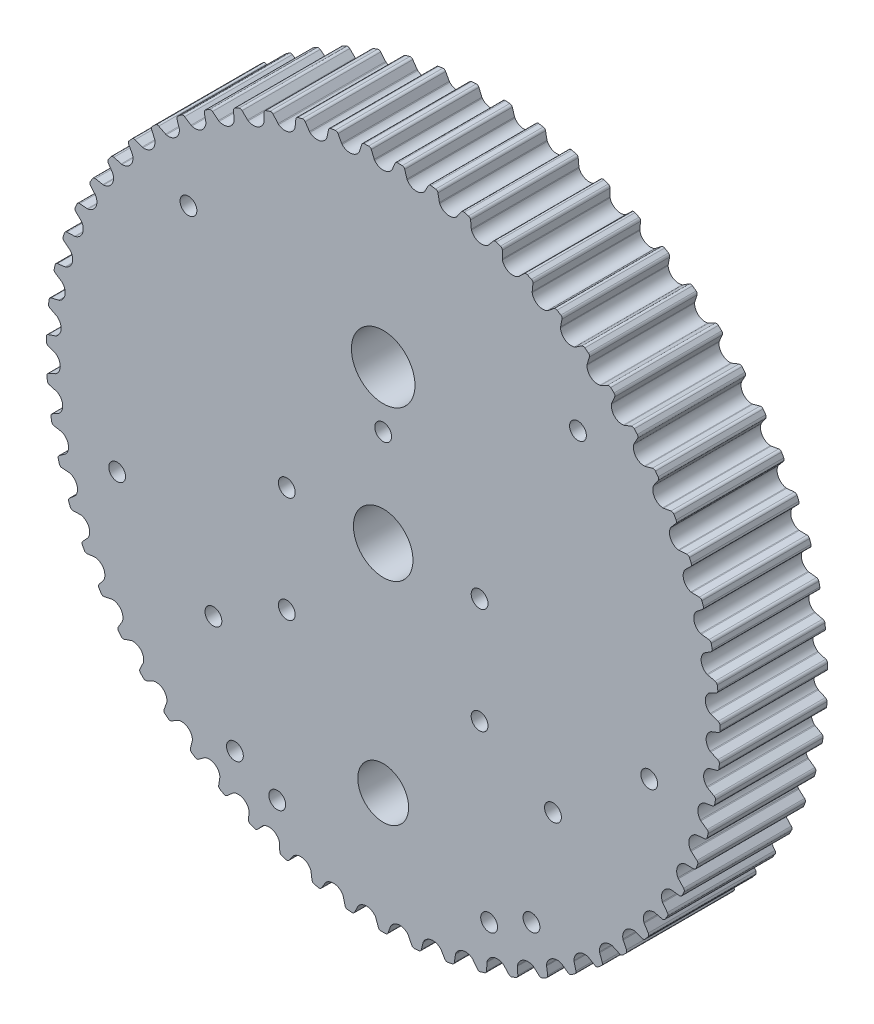
SolidWorks part; units mm, degrees
material "PETG"
ref_plane "Front Plane" through (0, 0, 0) normal (0, 0, 1) x (1, 0, 0)
ref_plane "Top Plane" through (0, 0, 0) normal (0, 1, 0) x (1, 0, 0)
ref_plane "Right Plane" through (0, 0, 0) normal (1, 0, 0) x (0, 0, -1)
sketch "Sketch1" plane through (0, 0, 0) normal (0, 0, 1) x (1, 0, 0)
  line L0 (0, 0) -> (0, 50000) construction
  line L1 (0, 0) -> (3.9983, 80.1144) construction
  line L2 (0, 0) -> (-3.9983, 80.1144) construction
  line L3 (-2.1085, 77.3973) -> (-2.8064, 79.0584)
  line L4 (2.1085, 77.3973) -> (2.8064, 79.0584)
  line L5 (5.6082, 77.2226) -> (5.0793, 78.9449)
  line L6 (9.8043, 76.8027) -> (10.6641, 78.3861)
  line L7 (13.2692, 76.2805) -> (12.9144, 78.0469)
  line L8 (17.4027, 75.4449) -> (18.4158, 76.9348)
  line L9 (20.7984, 74.5802) -> (20.6212, 76.3732)
  line L10 (24.8281, 73.3372) -> (25.9846, 74.7188)
  line L11 (28.1208, 72.1388) -> (28.123, 73.9405)
  line L12 (32.0068, 70.5007) -> (33.295, 71.7603)
  line L13 (35.1638, 68.9804) -> (35.3454, 70.7729)
  line L14 (38.8673, 66.9635) -> (40.2746, 68.0886)
  line L15 (41.8573, 65.1364) -> (42.2164, 66.902)
  line L16 (45.3416, 62.7608) -> (46.8539, 63.7402)
  line L17 (48.1348, 60.6451) -> (48.6679, 62.3661)
  line L18 (51.3652, 57.9344) -> (52.9675, 58.7583)
  line L19 (53.9339, 55.551) -> (54.6358, 57.2105)
  line L20 (56.8784, 52.5322) -> (58.5548, 53.1925)
  line L21 (59.197, 49.9049) -> (60.0606, 51.4862)
  line L22 (61.8263, 46.6079) -> (63.5601, 47.098)
  line L23 (63.8717, 43.7628) -> (64.8885, 45.2502)
  line L24 (66.1597, 40.2204) -> (67.9337, 40.5354)
  line L25 (67.9117, 37.1858) -> (69.0715, 38.5646)
  line L26 (69.8356, 33.4331) -> (71.6321, 33.57)
  line L27 (71.2767, 30.2392) -> (72.5681, 31.4956)
  line L28 (72.8174, 26.3136) -> (74.6186, 26.2709)
  line L29 (73.9334, 22.992) -> (75.3434, 24.1137)
  line L30 (75.0756, 18.9326) -> (76.8636, 18.7107)
  line L31 (75.8553, 15.5164) -> (77.37, 16.4921)
  line L32 (76.5876, 11.3634) -> (78.3446, 10.9646)
  line L33 (77.0233, 7.8865) -> (78.6276, 8.7066)
  line L34 (77.3384, 3.6813) -> (79.047, 3.1095)
  line L35 (77.4258, 0.1783) -> (79.1038, 0.8345)
  line L36 (77.3206, -4.0374) -> (78.9638, -4.7765)
  line L37 (77.0588, -7.5317) -> (78.7938, -7.0458)
  line L38 (76.5344, -11.716) -> (78.0959, -12.615)
  line L39 (75.9259, -15.1668) -> (77.7007, -14.8561)
  line L40 (74.9876, -19.2782) -> (76.4517, -20.3281)
  line L41 (74.0385, -22.6513) -> (75.8354, -22.5188)
  line L42 (72.6954, -26.6487) -> (74.0478, -27.8393)
  line L43 (71.4153, -29.9106) -> (73.2164, -29.9577)
  line L44 (69.6808, -33.7544) -> (70.908, -35.0737)
  line L45 (68.0823, -36.8726) -> (69.8697, -37.0988)
  line L46 (65.9737, -40.5247) -> (67.0634, -41.9596)
  line L47 (64.0726, -43.4682) -> (65.8287, -43.8712)
  line L48 (61.6109, -46.8922) -> (62.5523, -48.4284)
  line L49 (59.4262, -49.6317) -> (61.1334, -50.2076)
  line L50 (56.6358, -52.7936) -> (57.4196, -54.416)
  line L51 (54.1892, -55.302) -> (55.8306, -56.0451)
  line L52 (51.0978, -58.1704) -> (51.7161, -59.8627)
  line L53 (48.4136, -60.4227) -> (49.9728, -61.3255)
  line L54 (45.052, -62.969) -> (45.4988, -64.7145)
  line L55 (42.1568, -64.9429) -> (43.6185, -65.9965)
  line L56 (38.5585, -67.1418) -> (38.8292, -68.9231)
  line L57 (35.4811, -68.8177) -> (36.8306, -70.0115)
  line L58 (31.6817, -70.6474) -> (31.7737, -72.4468)
  line L59 (28.4528, -72.0085) -> (29.6767, -73.3307)
  line L60 (24.49, -73.4508) -> (24.4024, -75.2504)
  line L61 (21.1417, -74.4836) -> (22.2278, -75.9212)
  line L62 (17.055, -75.5242) -> (16.7887, -77.3062)
  line L63 (13.6204, -76.2185) -> (14.5581, -77.7571)
  line L64 (9.4505, -76.8471) -> (9.008, -78.5936)
  line L65 (5.9638, -77.1959) -> (6.7436, -78.8202)
  line L66 (1.752, -77.4061) -> (1.1379, -79.1)
  line L67 (-1.752, -77.4061) -> (-1.1379, -79.1)
  line L68 (-5.9638, -77.1959) -> (-6.7436, -78.8202)
  line L69 (-9.4505, -76.8471) -> (-9.008, -78.5936)
  line L70 (-13.6204, -76.2185) -> (-14.5581, -77.7571)
  line L71 (-17.055, -75.5242) -> (-16.7887, -77.3062)
  line L72 (-21.1417, -74.4836) -> (-22.2278, -75.9212)
  line L73 (-24.49, -73.4508) -> (-24.4024, -75.2504)
  line L74 (-28.4528, -72.0085) -> (-29.6767, -73.3307)
  line L75 (-31.6817, -70.6474) -> (-31.7737, -72.4468)
  line L76 (-35.4811, -68.8177) -> (-36.8306, -70.0115)
  line L77 (-38.5585, -67.1418) -> (-38.8292, -68.9231)
  line L78 (-42.1568, -64.9429) -> (-43.6185, -65.9965)
  line L79 (-45.052, -62.969) -> (-45.4988, -64.7145)
  line L80 (-48.4136, -60.4227) -> (-49.9728, -61.3255)
  line L81 (-51.0978, -58.1704) -> (-51.7161, -59.8627)
  line L82 (-54.1892, -55.302) -> (-55.8306, -56.0451)
  line L83 (-56.6358, -52.7936) -> (-57.4196, -54.416)
  line L84 (-59.4262, -49.6317) -> (-61.1334, -50.2076)
  line L85 (-61.6109, -46.8922) -> (-62.5523, -48.4284)
  line L86 (-64.0726, -43.4682) -> (-65.8287, -43.8712)
  line L87 (-65.9737, -40.5247) -> (-67.0634, -41.9596)
  line L88 (-68.0823, -36.8726) -> (-69.8697, -37.0988)
  line L89 (-69.6808, -33.7544) -> (-70.908, -35.0737)
  line L90 (-71.4153, -29.9106) -> (-73.2164, -29.9577)
  line L91 (-72.6954, -26.6487) -> (-74.0478, -27.8393)
  line L92 (-74.0385, -22.6513) -> (-75.8354, -22.5188)
  line L93 (-74.9876, -19.2782) -> (-76.4517, -20.3281)
  line L94 (-75.9259, -15.1668) -> (-77.7007, -14.8561)
  line L95 (-76.5344, -11.716) -> (-78.0959, -12.615)
  line L96 (-77.0588, -7.5317) -> (-78.7938, -7.0458)
  line L97 (-77.3206, -4.0374) -> (-78.9638, -4.7765)
  line L98 (-77.4258, 0.1783) -> (-79.1038, 0.8345)
  line L99 (-77.3384, 3.6813) -> (-79.047, 3.1095)
  line L100 (-77.0233, 7.8865) -> (-78.6276, 8.7066)
  line L101 (-76.5876, 11.3634) -> (-78.3446, 10.9646)
  line L102 (-75.8553, 15.5164) -> (-77.37, 16.4921)
  line L103 (-75.0756, 18.9326) -> (-76.8636, 18.7107)
  line L104 (-73.9334, 22.992) -> (-75.3434, 24.1137)
  line L105 (-72.8174, 26.3136) -> (-74.6186, 26.2709)
  line L106 (-71.2767, 30.2392) -> (-72.5681, 31.4956)
  line L107 (-69.8356, 33.4331) -> (-71.6321, 33.57)
  line L108 (-67.9117, 37.1858) -> (-69.0715, 38.5646)
  line L109 (-66.1597, 40.2204) -> (-67.9337, 40.5354)
  line L110 (-63.8717, 43.7628) -> (-64.8885, 45.2502)
  line L111 (-61.8263, 46.6079) -> (-63.5601, 47.098)
  line L112 (-59.197, 49.9049) -> (-60.0606, 51.4862)
  line L113 (-56.8784, 52.5322) -> (-58.5548, 53.1925)
  line L114 (-53.9339, 55.551) -> (-54.6358, 57.2105)
  line L115 (-51.3652, 57.9344) -> (-52.9675, 58.7583)
  line L116 (-48.1348, 60.6451) -> (-48.6679, 62.3661)
  line L117 (-45.3416, 62.7608) -> (-46.8539, 63.7402)
  line L118 (-41.8573, 65.1364) -> (-42.2164, 66.902)
  line L119 (-38.8673, 66.9635) -> (-40.2746, 68.0886)
  line L120 (-35.1638, 68.9804) -> (-35.3454, 70.7729)
  line L121 (-32.0068, 70.5007) -> (-33.295, 71.7603)
  line L122 (-28.1208, 72.1388) -> (-28.123, 73.9405)
  line L123 (0, 0) -> (2.0086, 77.226) construction
  line L124 (-24.8281, 73.3372) -> (-25.9846, 74.7188)
  line L125 (-20.7984, 74.5802) -> (-20.6212, 76.3732)
  line L126 (-17.4027, 75.4449) -> (-18.4158, 76.9348)
  line L127 (-13.2692, 76.2805) -> (-12.9144, 78.0469)
  line L128 (-9.8043, 76.8027) -> (-10.6641, 78.3861)
  line L129 (-5.6082, 77.2226) -> (-5.0793, 78.9449)
  circle A0 centre (0, 0) radius 80.2141 construction
  circle A317 centre (0, 0) radius 79.53 construction
  arc A318 (-2.0086, 77.226) -> (2.0086, 77.226) centre (0, 78.7807) ccw
  arc A319 (-2.0086, 77.226) -> (-2.1085, 77.3973) centre (-1.406, 77.6924) cw
  arc A320 (-2.8064, 79.0584) -> (-3.4334, 79.4559) centre (-3.4054, 78.8067) ccw
  arc A321 (-3.4334, 79.4559) -> (-3.9642, 79.4311) centre (0, 0) ccw
  arc A322 (3.4334, 79.4559) -> (3.9642, 79.4311) centre (0, 0) cw
  arc A323 (2.8064, 79.0584) -> (3.4334, 79.4559) centre (3.4054, 78.8067) cw
  arc A324 (2.0086, 77.226) -> (2.1085, 77.3973) centre (1.406, 77.6924) ccw
  arc A325 (4.4949, 79.4029) -> (3.9642, 79.4311) centre (0, 0) ccw
  arc A326 (5.0793, 78.9449) -> (4.4949, 79.4029) centre (4.4582, 78.7542) ccw
  arc A327 (5.6906, 77.0422) -> (9.6878, 76.6422) centre (7.844, 78.3892) ccw
  arc A328 (5.6906, 77.0422) -> (5.6082, 77.2226) centre (6.3366, 77.4463) cw
  arc A329 (9.6878, 76.6422) -> (9.8043, 76.8027) centre (9.1347, 77.1663) ccw
  arc A330 (10.6641, 78.3861) -> (11.3276, 78.7192) centre (11.2351, 78.0761) cw
  arc A331 (11.3276, 78.7192) -> (11.8533, 78.6417) centre (0, 0) cw
  arc A332 (12.3785, 78.5608) -> (11.8533, 78.6417) centre (0, 0) ccw
  arc A333 (12.9144, 78.0469) -> (12.3785, 78.5608) centre (12.2774, 77.919) ccw
  arc A334 (13.3333, 76.0928) -> (17.2708, 75.2968) centre (15.6101, 77.2187) ccw
  arc A335 (13.3333, 76.0928) -> (13.2692, 76.2805) centre (14.0163, 76.4305) cw
  arc A336 (17.2708, 75.2968) -> (17.4027, 75.4449) centre (16.7726, 75.8733) ccw
  arc A337 (18.4158, 76.9348) -> (19.1092, 77.2001) centre (18.9531, 76.5694) cw
  arc A338 (19.1092, 77.2001) -> (19.6246, 77.0707) centre (0, 0) cw
  arc A339 (20.1391, 76.9379) -> (19.6246, 77.0707) centre (0, 0) ccw
  arc A340 (20.6212, 76.3732) -> (20.1391, 76.9379) centre (19.9746, 76.3093) ccw
  arc A341 (20.8434, 74.3871) -> (24.6821, 73.203) centre (23.221, 75.2807) ccw
  arc A342 (20.8434, 74.3871) -> (20.7984, 74.5802) centre (21.5567, 74.6552) cw
  arc A343 (24.6821, 73.203) -> (24.8281, 73.3372) centre (24.2438, 73.8263) ccw
  arc A344 (25.9846, 74.7188) -> (26.7009, 74.9138) centre (26.4828, 74.3018) cw
  arc A345 (26.7009, 74.9138) -> (27.2009, 74.7338) centre (0, 0) cw
  arc A346 (27.6996, 74.5503) -> (27.2009, 74.7338) centre (0, 0) ccw
  arc A347 (28.123, 73.9405) -> (27.6996, 74.5503) centre (27.4733, 73.9413) ccw
  arc A348 (28.1464, 71.9421) -> (31.8481, 70.3817) centre (30.6012, 72.5945) ccw
  arc A349 (28.1464, 71.9421) -> (28.1208, 72.1388) centre (28.8828, 72.1378) cw
  arc A350 (31.8481, 70.3817) -> (32.0068, 70.5007) centre (31.474, 71.0455) ccw
  arc A351 (33.295, 71.7603) -> (34.0272, 71.883) centre (33.7493, 71.2958) cw
  arc A352 (34.0272, 71.883) -> (34.5068, 71.6541) centre (0, 0) cw
  arc A353 (34.9848, 71.4219) -> (34.5068, 71.6541) centre (0, 0) ccw
  arc A354 (35.3454, 70.7729) -> (34.9848, 71.4219) centre (34.699, 70.8384) ccw
  arc A355 (35.1696, 68.7821) -> (38.6976, 66.8609) centre (37.6772, 69.1869) ccw
  arc A356 (35.1696, 68.7821) -> (35.1638, 68.9804) centre (35.9219, 68.9036) cw
  arc A357 (38.6976, 66.8609) -> (38.8673, 66.9635) centre (38.3915, 67.5587) ccw
  arc A358 (40.2746, 68.0886) -> (41.0154, 68.1378) centre (40.6803, 67.5811) cw
  arc A359 (41.0154, 68.1378) -> (41.4697, 67.8622) centre (0, 0) cw
  arc A360 (41.9222, 67.5836) -> (41.4697, 67.8622) centre (0, 0) ccw
  arc A361 (42.2164, 66.902) -> (41.9222, 67.5836) centre (41.5798, 67.0315) ccw
  arc A362 (41.8434, 64.9386) -> (45.1625, 62.6756) centre (44.3787, 65.0917) ccw
  arc A363 (41.8434, 64.9386) -> (41.8573, 65.1364) centre (42.604, 64.9845) cw
  arc A364 (45.1625, 62.6756) -> (45.3416, 62.7608) centre (44.9274, 63.4004) ccw
  arc A365 (46.8539, 63.7402) -> (47.5959, 63.7154) centre (47.2071, 63.1949) cw
  arc A366 (47.5959, 63.7154) -> (48.0206, 63.3959) centre (0, 0) cw
  arc A367 (48.4431, 63.0737) -> (48.0206, 63.3959) centre (0, 0) ccw
  arc A368 (48.6679, 62.3661) -> (48.4431, 63.0737) centre (48.0473, 62.5584) ccw
  arc A369 (48.1012, 60.4496) -> (51.1786, 57.8674) centre (50.6393, 60.3495) ccw
  arc A370 (48.1012, 60.4496) -> (48.1348, 60.6451) centre (48.8626, 60.4196) cw
  arc A371 (51.1786, 57.8674) -> (51.3652, 57.9344) centre (51.0168, 58.6121) ccw
  arc A372 (52.9675, 58.7583) -> (53.7034, 58.6597) centre (53.2647, 58.1805) cw
  arc A373 (53.7034, 58.6597) -> (54.0941, 58.2996) centre (0, 0) cw
  arc A374 (54.4825, 57.9369) -> (54.0941, 58.2996) centre (0, 0) ccw
  arc A375 (54.6358, 57.2105) -> (54.4825, 57.9369) centre (54.0374, 57.4636) ccw
  arc A376 (53.881, 55.3599) -> (56.686, 52.4841) centre (56.3965, 55.0076) ccw
  arc A377 (53.881, 55.3599) -> (53.9339, 55.551) centre (54.6357, 55.2542) cw
  arc A378 (56.686, 52.4841) -> (56.8784, 52.5322) centre (56.5991, 53.2412) ccw
  arc A379 (58.5548, 53.1925) -> (59.2772, 53.0211) centre (58.7929, 52.588) cw
  arc A380 (59.2772, 53.0211) -> (59.6301, 52.6239) centre (0, 0) cw
  arc A381 (59.9804, 52.2243) -> (59.6301, 52.6239) centre (0, 0) ccw
  arc A382 (60.0606, 51.4862) -> (59.9804, 52.2243) centre (59.4904, 51.7976) ccw
  arc A383 (59.1254, 49.72) -> (61.63, 46.5792) centre (61.5932, 49.119) ccw
  arc A384 (59.1254, 49.72) -> (59.197, 49.9049) centre (59.8657, 49.5397) cw
  arc A385 (61.63, 46.5792) -> (61.8263, 46.6079) centre (61.619, 47.3411) ccw
  arc A386 (63.5601, 47.098) -> (64.2618, 46.8555) centre (63.7368, 46.4728) cw
  arc A387 (64.2618, 46.8555) -> (64.5734, 46.4251) centre (0, 0) cw
  arc A388 (64.8822, 45.9926) -> (64.5734, 46.4251) centre (0, 0) ccw
  arc A389 (64.8885, 45.2502) -> (64.8822, 45.9926) centre (64.3521, 45.6169) ccw
  arc A390 (63.7821, 43.5859) -> (65.9616, 40.2114) centre (66.1778, 42.7422) ccw
  arc A391 (63.7821, 43.5859) -> (63.8717, 43.7628) centre (64.5008, 43.3328) cw
  arc A392 (65.9616, 40.2114) -> (66.1597, 40.2204) centre (66.0264, 40.9706) ccw
  arc A393 (67.9337, 40.5354) -> (68.6078, 40.2243) centre (68.0473, 39.8957) cw
  arc A394 (68.6078, 40.2243) -> (68.875, 39.765) centre (0, 0) cw
  arc A395 (69.1392, 39.3039) -> (68.875, 39.765) centre (0, 0) ccw
  arc A396 (69.0715, 38.5646) -> (69.1392, 39.3039) centre (68.5743, 38.9828) ccw
  arc A397 (67.8049, 37.0187) -> (69.6375, 33.4439) centre (70.1047, 35.9406) ccw
  arc A398 (67.8049, 37.0187) -> (67.9117, 37.1858) centre (68.4948, 36.6953) cw
  arc A399 (69.6375, 33.4439) -> (69.8356, 33.4331) centre (69.7777, 34.1929) ccw
  arc A400 (71.6321, 33.57) -> (72.2719, 33.1933) centre (71.6815, 32.9221) cw
  arc A401 (72.2719, 33.1933) -> (72.4921, 32.7097) centre (0, 0) cw
  arc A402 (72.709, 32.2246) -> (72.4921, 32.7097) centre (0, 0) ccw
  arc A403 (72.5681, 31.4956) -> (72.709, 32.2246) centre (72.115, 31.9613) ccw
  arc A404 (71.1538, 30.0836) -> (72.6214, 26.3441) centre (73.3349, 28.7818) ccw
  arc A405 (71.1538, 30.0836) -> (71.2767, 30.2392) centre (71.8081, 29.693) cw
  arc A406 (72.6214, 26.3441) -> (72.8174, 26.3136) centre (72.8355, 27.0754) ccw
  arc A407 (74.6186, 26.2709) -> (75.2177, 25.8324) centre (74.6032, 25.6214) cw
  arc A408 (75.2177, 25.8324) -> (75.3887, 25.3292) centre (0, 0) cw
  arc A409 (75.5562, 24.825) -> (75.3887, 25.3292) centre (0, 0) ccw
  arc A410 (75.3434, 24.1137) -> (75.5562, 24.825) centre (74.939, 24.6222) ccw
  arc A411 (73.7956, 22.8494) -> (74.8836, 18.9824) centre (75.8362, 21.337) ccw
  arc A412 (73.7956, 22.8494) -> (73.9334, 22.992) centre (74.4078, 22.3957) cw
  arc A413 (74.8836, 18.9824) -> (75.0756, 18.9326) centre (75.1694, 19.6888) ccw
  arc A414 (76.8636, 18.7107) -> (77.416, 18.2148) centre (76.7836, 18.066) cw
  arc A415 (77.416, 18.2148) -> (77.536, 17.6971) centre (0, 0) cw
  arc A416 (77.6525, 17.1786) -> (77.536, 17.6971) centre (0, 0) ccw
  arc A417 (77.37, 16.4921) -> (77.6525, 17.1786) centre (77.0181, 17.0383) ccw
  arc A418 (75.7039, 15.3882) -> (76.4015, 11.4321) centre (77.5838, 13.6801) ccw
  arc A419 (75.7039, 15.3882) -> (75.8553, 15.5164) centre (76.2679, 14.8758) cw
  arc A420 (76.4015, 11.4321) -> (76.5876, 11.3634) centre (76.7562, 12.1065) ccw
  arc A421 (78.3446, 10.9646) -> (78.8449, 10.4161) centre (78.2008, 10.331) cw
  arc A422 (78.8449, 10.4161) -> (78.9128, 9.8891) centre (0, 0) cw
  arc A423 (78.9771, 9.3616) -> (78.9128, 9.8891) centre (0, 0) ccw
  arc A424 (78.6276, 8.7066) -> (78.9771, 9.3616) centre (78.3319, 9.2851) ccw
  arc A425 (76.8599, 7.7741) -> (77.1601, 3.7681) centre (78.5604, 5.8873) ccw
  arc A426 (76.8599, 7.7741) -> (77.0233, 7.8865) centre (77.3701, 7.208) cw
  arc A427 (77.1601, 3.7681) -> (77.3384, 3.6813) centre (77.5802, 4.4039) ccw
  arc A428 (79.047, 3.1095) -> (79.4903, 2.5139) centre (78.8409, 2.4934) cw
  arc A429 (79.4903, 2.5139) -> (79.5053, 1.9827) centre (0, 0) cw
  arc A430 (79.5168, 1.4515) -> (79.5053, 1.9827) centre (0, 0) ccw
  arc A431 (79.1038, 0.8345) -> (79.5168, 1.4515) centre (78.8671, 1.4396) ccw
  arc A432 (77.252, 0.0827) -> (77.1519, -3.9333) centre (78.7562, -1.9641) ccw
  arc A433 (77.252, 0.0827) -> (77.4258, 0.1783) centre (77.7033, -0.5314) cw
  arc A434 (77.1519, -3.9333) -> (77.3206, -4.0374) centre (77.6332, -3.3425) ccw
  arc A435 (78.9638, -4.7765) -> (79.3456, -5.4133) centre (78.6973, -5.369) cw
  arc A436 (79.3456, -5.4133) -> (79.3076, -5.9433) centre (0, 0) cw
  arc A437 (79.2661, -6.4731) -> (79.3076, -5.9433) centre (0, 0) ccw
  arc A438 (78.7938, -7.0458) -> (79.2661, -6.4731) centre (78.6186, -6.4202) ccw
  arc A439 (76.8764, -7.6096) -> (76.3769, -11.5956) centre (78.1693, -9.7959) ccw
  arc A440 (76.8764, -7.6096) -> (77.0588, -7.5317) centre (77.2643, -8.2655) cw
  arc A441 (76.3769, -11.5956) -> (76.5344, -11.716) centre (76.9146, -11.0557) ccw
  arc A442 (78.0959, -12.615) -> (78.4123, -13.2866) centre (77.7717, -13.1781) cw
  arc A443 (78.4123, -13.2866) -> (78.3218, -13.8102) centre (0, 0) cw
  arc A444 (78.2277, -14.3332) -> (78.3218, -13.8102) centre (0, 0) ccw
  arc A445 (77.7007, -14.8561) -> (78.2277, -14.3332) centre (77.5887, -14.2161) ccw
  arc A446 (75.7367, -15.2262) -> (74.8428, -19.1426) centre (76.8055, -17.5304) ccw
  arc A447 (75.7367, -15.2262) -> (75.9259, -15.1668) centre (76.0573, -15.9174) cw
  arc A448 (74.8428, -19.1426) -> (74.9876, -19.2782) centre (75.4316, -18.6589) ccw
  arc A449 (76.4517, -20.3281) -> (76.6997, -21.0279) centre (76.0731, -20.8561) cw
  arc A450 (76.6997, -21.0279) -> (76.5575, -21.5399) centre (0, 0) cw
  arc A451 (76.4119, -22.051) -> (76.5575, -21.5399) centre (0, 0) ccw
  arc A452 (75.8354, -22.5188) -> (76.4119, -22.051) centre (75.7876, -21.8708) ccw
  arc A453 (73.8443, -22.6914) -> (72.5649, -26.4994) centre (74.6784, -25.0906) ccw
  arc A454 (73.8443, -22.6914) -> (74.0385, -22.6513) centre (74.0945, -23.4112) cw
  arc A455 (72.5649, -26.4994) -> (72.6954, -26.6487) centre (73.1989, -26.0768) ccw
  arc A456 (74.0478, -27.8393) -> (74.2249, -28.5603) centre (73.6185, -28.3269) cw
  arc A457 (74.2249, -28.5603) -> (74.0324, -29.0556) centre (0, 0) cw
  arc A458 (73.8366, -29.5496) -> (74.0324, -29.0556) centre (0, 0) ccw
  arc A459 (73.2164, -29.9577) -> (73.8366, -29.5496) centre (73.2334, -29.3082) ccw
  arc A460 (71.218, -29.9312) -> (69.5658, -33.5929) centre (71.8091, -32.4015) ccw
  arc A461 (71.218, -29.9312) -> (71.4153, -29.9106) centre (71.3953, -30.6723) cw
  arc A462 (69.5658, -33.5929) -> (69.6808, -33.7544) centre (70.2388, -33.2355) ccw
  arc A463 (70.908, -35.0737) -> (71.0123, -35.8088) centre (70.4322, -35.5162) cw
  arc A464 (71.0123, -35.8088) -> (70.7715, -36.2824) centre (0, 0) cw
  arc A465 (70.5275, -36.7545) -> (70.7715, -36.2824) centre (0, 0) ccw
  arc A466 (69.8697, -37.0988) -> (70.5275, -36.7545) centre (69.9513, -36.4542) ccw
  arc A467 (67.8839, -36.8735) -> (65.8754, -40.3525) centre (68.2261, -39.3903) ccw
  arc A468 (67.8839, -36.8735) -> (68.0823, -36.8726) centre (67.9866, -37.6286) cw
  arc A469 (65.8754, -40.3525) -> (65.9737, -40.5247) centre (66.5806, -40.0638) ccw
  arc A470 (67.0634, -41.9596) -> (67.0941, -42.7014) centre (66.5459, -42.3525) cw
  arc A471 (67.0941, -42.7014) -> (66.8073, -43.1487) centre (0, 0) cw
  arc A472 (66.5175, -43.5941) -> (66.8073, -43.1487) centre (0, 0) ccw
  arc A473 (65.8287, -43.8712) -> (66.5175, -43.5941) centre (65.974, -43.238) ccw
  arc A474 (63.8752, -43.4493) -> (61.5302, -46.711) centre (63.965, -45.9877) ccw
  arc A475 (63.8752, -43.4493) -> (64.0726, -43.4682) centre (63.9021, -44.2108) cw
  arc A476 (61.5302, -46.711) -> (61.6109, -46.8922) centre (62.2607, -46.494) ccw
  arc A477 (62.5523, -48.4284) -> (62.509, -49.1696) centre (61.9983, -48.7679) cw
  arc A478 (62.509, -49.1696) -> (62.1791, -49.5861) centre (0, 0) cw
  arc A479 (61.8464, -50.0005) -> (62.1791, -49.5861) centre (0, 0) ccw
  arc A480 (61.1334, -50.2076) -> (61.8464, -50.0005) centre (61.3411, -49.592) ccw
  arc A481 (59.2316, -49.5933) -> (56.5735, -52.6053) centre (59.0683, -52.1281) ccw
  arc A482 (59.2316, -49.5933) -> (59.4262, -49.6317) centre (59.1826, -50.3538) cw
  arc A483 (56.5735, -52.6053) -> (56.6358, -52.7936) centre (57.322, -52.4621) ccw
  arc A484 (57.4196, -54.416) -> (57.3027, -55.1491) centre (56.8345, -54.6986) cw
  arc A485 (57.3027, -55.1491) -> (56.9329, -55.5308) centre (0, 0) cw
  arc A486 (56.5606, -55.9099) -> (56.9329, -55.5308) centre (0, 0) ccw
  arc A487 (55.8306, -56.0451) -> (56.5606, -55.9099) centre (56.0985, -55.4532) ccw
  arc A488 (53.9994, -55.2445) -> (51.0546, -57.9768) centre (53.5845, -57.7503) ccw
  arc A489 (53.9994, -55.2445) -> (54.1892, -55.302) centre (53.8749, -55.9962) cw
  arc A490 (51.0546, -57.9768) -> (51.0978, -58.1704) centre (51.8136, -57.9089) ccw
  arc A491 (51.7161, -59.8627) -> (51.5268, -60.5806) centre (51.1059, -60.0857) cw
  arc A492 (51.5268, -60.5806) -> (51.1209, -60.9235) centre (0, 0) cw
  arc A493 (50.7127, -61.2637) -> (51.1209, -60.9235) centre (0, 0) ccw
  arc A494 (49.9728, -61.3255) -> (50.7127, -61.2637) centre (50.2984, -60.7632) ccw
  arc A495 (48.2305, -60.3465) -> (45.0283, -62.7721) centre (47.5681, -62.7987) ccw
  arc A496 (48.2305, -60.3465) -> (48.4136, -60.4227) centre (48.0318, -61.0822) cw
  arc A497 (45.0283, -62.7721) -> (45.052, -62.969) centre (45.7902, -62.7801) ccw
  arc A498 (45.4988, -64.7145) -> (45.2389, -65.41) centre (44.8693, -64.8756) cw
  arc A499 (45.2389, -65.41) -> (44.8008, -65.7108) centre (0, 0) cw
  arc A500 (44.3608, -66.0086) -> (44.8008, -65.7108) centre (0, 0) ccw
  arc A501 (43.6185, -65.9965) -> (44.3608, -66.0086) centre (43.9984, -65.4694) ccw
  arc A502 (41.9822, -64.8489) -> (38.5544, -66.9436) centre (41.079, -67.2229) ccw
  arc A503 (41.9822, -64.8489) -> (42.1568, -64.9429) centre (41.7113, -65.5611) cw
  arc A504 (38.5544, -66.9436) -> (38.5585, -67.1418) centre (39.3118, -67.0273) ccw
  arc A505 (38.8292, -68.9231) -> (38.5014, -69.5893) centre (38.1868, -69.0208) cw
  arc A506 (38.5014, -69.5893) -> (38.0355, -69.845) centre (0, 0) cw
  arc A507 (37.568, -70.0975) -> (38.0355, -69.845) centre (0, 0) ccw
  arc A508 (36.8306, -70.0115) -> (37.568, -70.0975) centre (37.2611, -69.5249) ccw
  arc A509 (35.3168, -68.7067) -> (31.6974, -70.4497) centre (34.1817, -70.979) ccw
  arc A510 (35.3168, -68.7067) -> (35.4811, -68.8177) centre (34.9762, -69.3884) cw
  arc A511 (31.6974, -70.4497) -> (31.6817, -70.6474) centre (32.4427, -70.6085) ccw
  arc A512 (31.7737, -72.4468) -> (31.3812, -73.077) centre (31.1248, -72.48) cw
  arc A513 (31.3812, -73.077) -> (30.8922, -73.285) centre (0, 0) cw
  arc A514 (30.4019, -73.4898) -> (30.8922, -73.285) centre (0, 0) ccw
  arc A515 (29.6767, -73.3307) -> (30.4019, -73.4898) centre (30.1535, -72.8894) ccw
  arc A516 (28.3003, -71.8817) -> (24.5254, -73.2556) centre (26.9446, -74.0296) ccw
  arc A517 (28.3003, -71.8817) -> (28.4528, -72.0085) centre (27.8936, -72.5261) cw
  arc A518 (24.5254, -73.2556) -> (24.49, -73.4508) centre (25.2511, -73.4878) ccw
  arc A519 (24.4024, -75.2504) -> (23.9491, -75.8384) centre (23.7535, -75.2188) cw
  arc A520 (23.9491, -75.8384) -> (23.4419, -75.9967) centre (0, 0) cw
  arc A521 (22.9336, -76.1516) -> (23.4419, -75.9967) centre (0, 0) ccw
  arc A522 (22.2278, -75.9212) -> (22.9336, -76.1516) centre (22.7462, -75.5295) ccw
  arc A523 (21.0026, -74.3423) -> (17.1096, -75.3336) centre (19.4397, -76.3446) ccw
  arc A524 (21.0026, -74.3423) -> (21.1417, -74.4836) centre (20.5337, -74.943) cw
  arc A525 (17.1096, -75.3336) -> (17.055, -75.5242) centre (17.8086, -75.6369) ccw
  arc A526 (16.7887, -77.3062) -> (16.2791, -77.8461) centre (16.1461, -77.2101) cw
  arc A527 (16.2791, -77.8461) -> (15.7586, -77.9531) centre (0, 0) cw
  arc A528 (15.2374, -78.0567) -> (15.7586, -77.9531) centre (0, 0) ccw
  arc A529 (14.5581, -77.7571) -> (15.2374, -78.0567) centre (15.1129, -77.419) ccw
  arc A530 (13.4961, -76.0641) -> (9.5238, -76.6628) centre (11.7417, -77.9008) ccw
  arc A531 (13.4961, -76.0641) -> (13.6204, -76.2185) centre (12.9698, -76.6151) cw
  arc A532 (9.5238, -76.6628) -> (9.4505, -76.8471) centre (10.1891, -77.0342) ccw
  arc A533 (9.008, -78.5936) -> (8.4472, -79.0801) centre (8.3782, -78.4341) cw
  arc A534 (8.4472, -79.0801) -> (7.9186, -79.1348) centre (0, 0) cw
  arc A535 (7.3897, -79.1859) -> (7.9186, -79.1348) centre (0, 0) ccw
  arc A536 (6.7436, -78.8202) -> (7.3897, -79.1859) centre (7.3293, -78.539) ccw
  arc A537 (5.8555, -77.0298) -> (1.8433, -77.2301) centre (3.9269, -78.6828) ccw
  arc A538 (5.8555, -77.0298) -> (5.9638, -77.1959) centre (5.2769, -77.5257) cw
  arc A539 (1.8433, -77.2301) -> (1.752, -77.4061) centre (2.4684, -77.6659) ccw
  arc A540 (1.1379, -79.1) -> (0.5314, -79.5282) centre (0.527, -78.8785) cw
  arc A541 (0.5314, -79.5282) -> (0, -79.53) centre (0, 0) cw
  arc A542 (-0.5314, -79.5282) -> (0, -79.53) centre (0, 0) ccw
  arc A543 (-1.1379, -79.1) -> (-0.5314, -79.5282) centre (-0.527, -78.8785) ccw
  arc A544 (-1.8433, -77.2301) -> (-5.8555, -77.0298) centre (-3.9269, -78.6828) ccw
  arc A545 (-1.8433, -77.2301) -> (-1.752, -77.4061) centre (-2.4684, -77.6659) cw
  arc A546 (-5.8555, -77.0298) -> (-5.9638, -77.1959) centre (-5.2769, -77.5257) ccw
  arc A547 (-6.7436, -78.8202) -> (-7.3897, -79.1859) centre (-7.3293, -78.539) cw
  arc A548 (-7.3897, -79.1859) -> (-7.9186, -79.1348) centre (0, 0) cw
  arc A549 (-8.4472, -79.0801) -> (-7.9186, -79.1348) centre (0, 0) ccw
  arc A550 (-9.008, -78.5936) -> (-8.4472, -79.0801) centre (-8.3782, -78.4341) ccw
  arc A551 (-9.5238, -76.6628) -> (-13.4961, -76.0641) centre (-11.7417, -77.9008) ccw
  arc A552 (-9.5238, -76.6628) -> (-9.4505, -76.8471) centre (-10.1891, -77.0342) cw
  arc A553 (-13.4961, -76.0641) -> (-13.6204, -76.2185) centre (-12.9698, -76.6151) ccw
  arc A554 (-14.5581, -77.7571) -> (-15.2374, -78.0567) centre (-15.1129, -77.419) cw
  arc A555 (-15.2374, -78.0567) -> (-15.7586, -77.9531) centre (0, 0) cw
  arc A556 (-16.2791, -77.8461) -> (-15.7586, -77.9531) centre (0, 0) ccw
  arc A557 (-16.7887, -77.3062) -> (-16.2791, -77.8461) centre (-16.1461, -77.2101) ccw
  arc A558 (-17.1096, -75.3336) -> (-21.0026, -74.3423) centre (-19.4397, -76.3446) ccw
  arc A559 (-17.1096, -75.3336) -> (-17.055, -75.5242) centre (-17.8086, -75.6369) cw
  arc A560 (-21.0026, -74.3423) -> (-21.1417, -74.4836) centre (-20.5337, -74.943) ccw
  arc A561 (-22.2278, -75.9212) -> (-22.9336, -76.1516) centre (-22.7462, -75.5295) cw
  arc A562 (-22.9336, -76.1516) -> (-23.4419, -75.9967) centre (0, 0) cw
  arc A563 (-23.9491, -75.8384) -> (-23.4419, -75.9967) centre (0, 0) ccw
  arc A564 (-24.4024, -75.2504) -> (-23.9491, -75.8384) centre (-23.7535, -75.2188) ccw
  arc A565 (-24.5254, -73.2556) -> (-28.3003, -71.8817) centre (-26.9446, -74.0296) ccw
  arc A566 (-24.5254, -73.2556) -> (-24.49, -73.4508) centre (-25.2511, -73.4878) cw
  arc A567 (-28.3003, -71.8817) -> (-28.4528, -72.0085) centre (-27.8936, -72.5261) ccw
  arc A568 (-29.6767, -73.3307) -> (-30.4019, -73.4898) centre (-30.1535, -72.8894) cw
  arc A569 (-30.4019, -73.4898) -> (-30.8922, -73.285) centre (0, 0) cw
  arc A570 (-31.3812, -73.077) -> (-30.8922, -73.285) centre (0, 0) ccw
  arc A571 (-31.7737, -72.4468) -> (-31.3812, -73.077) centre (-31.1248, -72.48) ccw
  arc A572 (-31.6974, -70.4497) -> (-35.3168, -68.7067) centre (-34.1817, -70.979) ccw
  arc A573 (-31.6974, -70.4497) -> (-31.6817, -70.6474) centre (-32.4427, -70.6085) cw
  arc A574 (-35.3168, -68.7067) -> (-35.4811, -68.8177) centre (-34.9762, -69.3884) ccw
  arc A575 (-36.8306, -70.0115) -> (-37.568, -70.0975) centre (-37.2611, -69.5249) cw
  arc A576 (-37.568, -70.0975) -> (-38.0355, -69.845) centre (0, 0) cw
  arc A577 (-38.5014, -69.5893) -> (-38.0355, -69.845) centre (0, 0) ccw
  arc A578 (-38.8292, -68.9231) -> (-38.5014, -69.5893) centre (-38.1868, -69.0208) ccw
  arc A579 (-38.5544, -66.9436) -> (-41.9822, -64.8489) centre (-41.079, -67.2229) ccw
  arc A580 (-38.5544, -66.9436) -> (-38.5585, -67.1418) centre (-39.3118, -67.0273) cw
  arc A581 (-41.9822, -64.8489) -> (-42.1568, -64.9429) centre (-41.7113, -65.5611) ccw
  arc A582 (-43.6185, -65.9965) -> (-44.3608, -66.0086) centre (-43.9984, -65.4694) cw
  arc A583 (-44.3608, -66.0086) -> (-44.8008, -65.7108) centre (0, 0) cw
  arc A584 (-45.2389, -65.41) -> (-44.8008, -65.7108) centre (0, 0) ccw
  arc A585 (-45.4988, -64.7145) -> (-45.2389, -65.41) centre (-44.8693, -64.8756) ccw
  arc A586 (-45.0283, -62.7721) -> (-48.2305, -60.3465) centre (-47.5681, -62.7987) ccw
  arc A587 (-45.0283, -62.7721) -> (-45.052, -62.969) centre (-45.7902, -62.7801) cw
  arc A588 (-48.2305, -60.3465) -> (-48.4136, -60.4227) centre (-48.0318, -61.0822) ccw
  arc A589 (-49.9728, -61.3255) -> (-50.7127, -61.2637) centre (-50.2984, -60.7632) cw
  arc A590 (-50.7127, -61.2637) -> (-51.1209, -60.9235) centre (0, 0) cw
  arc A591 (-51.5268, -60.5806) -> (-51.1209, -60.9235) centre (0, 0) ccw
  arc A592 (-51.7161, -59.8627) -> (-51.5268, -60.5806) centre (-51.1059, -60.0857) ccw
  arc A593 (-51.0546, -57.9768) -> (-53.9994, -55.2445) centre (-53.5845, -57.7503) ccw
  arc A594 (-51.0546, -57.9768) -> (-51.0978, -58.1704) centre (-51.8136, -57.9089) cw
  arc A595 (-53.9994, -55.2445) -> (-54.1892, -55.302) centre (-53.8749, -55.9962) ccw
  arc A596 (-55.8306, -56.0451) -> (-56.5606, -55.9099) centre (-56.0985, -55.4532) cw
  arc A597 (-56.5606, -55.9099) -> (-56.9329, -55.5308) centre (0, 0) cw
  arc A598 (-57.3027, -55.1491) -> (-56.9329, -55.5308) centre (0, 0) ccw
  arc A599 (-57.4196, -54.416) -> (-57.3027, -55.1491) centre (-56.8345, -54.6986) ccw
  arc A600 (-56.5735, -52.6053) -> (-59.2316, -49.5933) centre (-59.0683, -52.1281) ccw
  arc A601 (-56.5735, -52.6053) -> (-56.6358, -52.7936) centre (-57.322, -52.4621) cw
  arc A602 (-59.2316, -49.5933) -> (-59.4262, -49.6317) centre (-59.1826, -50.3538) ccw
  arc A603 (-61.1334, -50.2076) -> (-61.8464, -50.0005) centre (-61.3411, -49.592) cw
  arc A604 (-61.8464, -50.0005) -> (-62.1791, -49.5861) centre (0, 0) cw
  arc A605 (-62.509, -49.1696) -> (-62.1791, -49.5861) centre (0, 0) ccw
  arc A606 (-62.5523, -48.4284) -> (-62.509, -49.1696) centre (-61.9983, -48.7679) ccw
  arc A607 (-61.5302, -46.711) -> (-63.8752, -43.4493) centre (-63.965, -45.9877) ccw
  arc A608 (-61.5302, -46.711) -> (-61.6109, -46.8922) centre (-62.2607, -46.494) cw
  arc A609 (-63.8752, -43.4493) -> (-64.0726, -43.4682) centre (-63.9021, -44.2108) ccw
  arc A610 (-65.8287, -43.8712) -> (-66.5175, -43.5941) centre (-65.974, -43.238) cw
  arc A611 (-66.5175, -43.5941) -> (-66.8073, -43.1487) centre (0, 0) cw
  arc A612 (-67.0941, -42.7014) -> (-66.8073, -43.1487) centre (0, 0) ccw
  arc A613 (-67.0634, -41.9596) -> (-67.0941, -42.7014) centre (-66.5459, -42.3525) ccw
  arc A614 (-65.8754, -40.3525) -> (-67.8839, -36.8735) centre (-68.2261, -39.3904) ccw
  arc A615 (-65.8754, -40.3525) -> (-65.9737, -40.5247) centre (-66.5806, -40.0638) cw
  arc A616 (-67.8839, -36.8735) -> (-68.0823, -36.8726) centre (-67.9866, -37.6286) ccw
  arc A617 (-69.8697, -37.0988) -> (-70.5275, -36.7545) centre (-69.9513, -36.4542) cw
  arc A618 (-70.5275, -36.7545) -> (-70.7715, -36.2824) centre (0, 0) cw
  arc A619 (-71.0123, -35.8088) -> (-70.7715, -36.2824) centre (0, 0) ccw
  arc A620 (-70.908, -35.0737) -> (-71.0123, -35.8088) centre (-70.4322, -35.5162) ccw
  arc A621 (-69.5658, -33.5929) -> (-71.218, -29.9312) centre (-71.8091, -32.4015) ccw
  arc A622 (-69.5658, -33.5929) -> (-69.6808, -33.7544) centre (-70.2388, -33.2355) cw
  arc A623 (-71.218, -29.9312) -> (-71.4153, -29.9106) centre (-71.3953, -30.6723) ccw
  arc A624 (-73.2164, -29.9577) -> (-73.8366, -29.5496) centre (-73.2334, -29.3082) cw
  arc A625 (-73.8366, -29.5496) -> (-74.0324, -29.0556) centre (0, 0) cw
  arc A626 (-74.2249, -28.5603) -> (-74.0324, -29.0556) centre (0, 0) ccw
  arc A627 (-74.0478, -27.8393) -> (-74.2249, -28.5603) centre (-73.6185, -28.3269) ccw
  arc A628 (-72.5649, -26.4994) -> (-73.8443, -22.6914) centre (-74.6784, -25.0906) ccw
  arc A629 (-72.5649, -26.4994) -> (-72.6954, -26.6487) centre (-73.1989, -26.0768) cw
  arc A630 (-73.8443, -22.6914) -> (-74.0385, -22.6513) centre (-74.0945, -23.4112) ccw
  arc A631 (-75.8354, -22.5188) -> (-76.4119, -22.051) centre (-75.7876, -21.8708) cw
  arc A632 (-76.4119, -22.051) -> (-76.5575, -21.5399) centre (0, 0) cw
  arc A633 (-76.6997, -21.0279) -> (-76.5575, -21.5399) centre (0, 0) ccw
  arc A634 (-76.4517, -20.3281) -> (-76.6997, -21.0279) centre (-76.0731, -20.8561) ccw
  arc A635 (-74.8428, -19.1426) -> (-75.7367, -15.2262) centre (-76.8055, -17.5304) ccw
  arc A636 (-74.8428, -19.1426) -> (-74.9876, -19.2782) centre (-75.4316, -18.6589) cw
  arc A637 (-75.7367, -15.2262) -> (-75.9259, -15.1668) centre (-76.0573, -15.9174) ccw
  arc A638 (-77.7007, -14.8561) -> (-78.2277, -14.3332) centre (-77.5887, -14.2161) cw
  arc A639 (-78.2277, -14.3332) -> (-78.3218, -13.8102) centre (0, 0) cw
  arc A640 (-78.4123, -13.2866) -> (-78.3218, -13.8102) centre (0, 0) ccw
  arc A641 (-78.0959, -12.615) -> (-78.4123, -13.2866) centre (-77.7717, -13.1781) ccw
  arc A642 (-76.3769, -11.5956) -> (-76.8764, -7.6096) centre (-78.1693, -9.7959) ccw
  arc A643 (-76.3769, -11.5956) -> (-76.5344, -11.716) centre (-76.9146, -11.0557) cw
  arc A644 (-76.8764, -7.6096) -> (-77.0588, -7.5317) centre (-77.2643, -8.2655) ccw
  arc A645 (-78.7938, -7.0458) -> (-79.2661, -6.4731) centre (-78.6186, -6.4202) cw
  arc A646 (-79.2661, -6.4731) -> (-79.3076, -5.9433) centre (0, 0) cw
  arc A647 (-79.3456, -5.4133) -> (-79.3076, -5.9433) centre (0, 0) ccw
  arc A648 (-78.9638, -4.7765) -> (-79.3456, -5.4133) centre (-78.6973, -5.369) ccw
  arc A649 (-77.1519, -3.9333) -> (-77.252, 0.0827) centre (-78.7562, -1.9641) ccw
  arc A650 (-77.1519, -3.9333) -> (-77.3206, -4.0374) centre (-77.6332, -3.3425) cw
  arc A651 (-77.252, 0.0827) -> (-77.4258, 0.1783) centre (-77.7033, -0.5314) ccw
  arc A652 (-79.1038, 0.8345) -> (-79.5168, 1.4515) centre (-78.8671, 1.4396) cw
  arc A653 (-79.5168, 1.4515) -> (-79.5053, 1.9827) centre (0, 0) cw
  arc A654 (-79.4903, 2.5139) -> (-79.5053, 1.9827) centre (0, 0) ccw
  arc A655 (-79.047, 3.1095) -> (-79.4903, 2.5139) centre (-78.8409, 2.4934) ccw
  arc A656 (-77.1601, 3.7681) -> (-76.8599, 7.7741) centre (-78.5604, 5.8873) ccw
  arc A657 (-77.1601, 3.7681) -> (-77.3384, 3.6813) centre (-77.5802, 4.4039) cw
  arc A658 (-76.8599, 7.7741) -> (-77.0233, 7.8865) centre (-77.3701, 7.208) ccw
  arc A659 (-78.6276, 8.7066) -> (-78.9771, 9.3616) centre (-78.3319, 9.2851) cw
  arc A660 (-78.9771, 9.3616) -> (-78.9128, 9.8891) centre (0, 0) cw
  arc A661 (-78.8449, 10.4161) -> (-78.9128, 9.8891) centre (0, 0) ccw
  arc A662 (-78.3446, 10.9646) -> (-78.8449, 10.4161) centre (-78.2008, 10.331) ccw
  arc A663 (-76.4015, 11.4321) -> (-75.7039, 15.3882) centre (-77.5838, 13.6801) ccw
  arc A664 (-76.4015, 11.4321) -> (-76.5876, 11.3634) centre (-76.7562, 12.1065) cw
  arc A665 (-75.7039, 15.3882) -> (-75.8553, 15.5164) centre (-76.2679, 14.8758) ccw
  arc A666 (-77.37, 16.4921) -> (-77.6525, 17.1786) centre (-77.0181, 17.0383) cw
  arc A667 (-77.6525, 17.1786) -> (-77.536, 17.6971) centre (0, 0) cw
  arc A668 (-77.416, 18.2148) -> (-77.536, 17.6971) centre (0, 0) ccw
  arc A669 (-76.8636, 18.7107) -> (-77.416, 18.2148) centre (-76.7836, 18.066) ccw
  arc A670 (-74.8836, 18.9824) -> (-73.7956, 22.8494) centre (-75.8362, 21.337) ccw
  arc A671 (-74.8836, 18.9824) -> (-75.0756, 18.9326) centre (-75.1694, 19.6888) cw
  arc A672 (-73.7956, 22.8494) -> (-73.9334, 22.992) centre (-74.4078, 22.3957) ccw
  arc A673 (-75.3434, 24.1137) -> (-75.5562, 24.825) centre (-74.939, 24.6222) cw
  arc A674 (-75.5562, 24.825) -> (-75.3887, 25.3292) centre (0, 0) cw
  arc A675 (-75.2177, 25.8324) -> (-75.3887, 25.3292) centre (0, 0) ccw
  arc A676 (-74.6186, 26.2709) -> (-75.2177, 25.8324) centre (-74.6032, 25.6214) ccw
  arc A677 (-72.6214, 26.3441) -> (-71.1538, 30.0836) centre (-73.3349, 28.7818) ccw
  arc A678 (-72.6214, 26.3441) -> (-72.8174, 26.3136) centre (-72.8355, 27.0754) cw
  arc A679 (-71.1538, 30.0836) -> (-71.2767, 30.2392) centre (-71.8081, 29.693) ccw
  arc A680 (-72.5681, 31.4956) -> (-72.709, 32.2246) centre (-72.115, 31.9613) cw
  arc A681 (-72.709, 32.2246) -> (-72.4921, 32.7097) centre (0, 0) cw
  arc A682 (-72.2719, 33.1933) -> (-72.4921, 32.7097) centre (0, 0) ccw
  arc A683 (-71.6321, 33.57) -> (-72.2719, 33.1933) centre (-71.6815, 32.9221) ccw
  arc A684 (-69.6375, 33.4439) -> (-67.8049, 37.0187) centre (-70.1047, 35.9406) ccw
  arc A685 (-69.6375, 33.4439) -> (-69.8356, 33.4331) centre (-69.7777, 34.1929) cw
  arc A686 (-67.8049, 37.0187) -> (-67.9117, 37.1858) centre (-68.4948, 36.6953) ccw
  arc A687 (-69.0715, 38.5646) -> (-69.1392, 39.3039) centre (-68.5743, 38.9828) cw
  arc A688 (-69.1392, 39.3039) -> (-68.875, 39.765) centre (0, 0) cw
  arc A689 (-68.6078, 40.2243) -> (-68.875, 39.765) centre (0, 0) ccw
  arc A690 (-67.9337, 40.5354) -> (-68.6078, 40.2243) centre (-68.0473, 39.8957) ccw
  arc A691 (-65.9616, 40.2114) -> (-63.7821, 43.5859) centre (-66.1778, 42.7422) ccw
  arc A692 (-65.9616, 40.2114) -> (-66.1597, 40.2204) centre (-66.0264, 40.9706) cw
  arc A693 (-63.7821, 43.5859) -> (-63.8717, 43.7628) centre (-64.5008, 43.3328) ccw
  arc A694 (-64.8885, 45.2502) -> (-64.8822, 45.9926) centre (-64.3521, 45.6169) cw
  arc A695 (-64.8822, 45.9926) -> (-64.5734, 46.4251) centre (0, 0) cw
  arc A696 (-64.2618, 46.8555) -> (-64.5734, 46.4251) centre (0, 0) ccw
  arc A697 (-63.5601, 47.098) -> (-64.2618, 46.8555) centre (-63.7368, 46.4728) ccw
  arc A698 (-61.63, 46.5792) -> (-59.1254, 49.72) centre (-61.5932, 49.119) ccw
  arc A699 (-61.63, 46.5792) -> (-61.8263, 46.6079) centre (-61.619, 47.3411) cw
  arc A700 (-59.1254, 49.72) -> (-59.197, 49.9049) centre (-59.8657, 49.5397) ccw
  arc A701 (-60.0606, 51.4862) -> (-59.9804, 52.2243) centre (-59.4904, 51.7976) cw
  arc A702 (-59.9804, 52.2243) -> (-59.6301, 52.6239) centre (0, 0) cw
  arc A703 (-59.2772, 53.0211) -> (-59.6301, 52.6239) centre (0, 0) ccw
  arc A704 (-58.5548, 53.1925) -> (-59.2772, 53.0211) centre (-58.7929, 52.588) ccw
  arc A705 (-56.686, 52.4841) -> (-53.881, 55.3599) centre (-56.3965, 55.0076) ccw
  arc A706 (-56.686, 52.4841) -> (-56.8784, 52.5322) centre (-56.5991, 53.2412) cw
  arc A707 (-53.881, 55.3599) -> (-53.9339, 55.551) centre (-54.6357, 55.2542) ccw
  arc A708 (-54.6358, 57.2105) -> (-54.4825, 57.9369) centre (-54.0374, 57.4636) cw
  arc A709 (-54.4825, 57.9369) -> (-54.0941, 58.2996) centre (0, 0) cw
  arc A710 (-53.7034, 58.6597) -> (-54.0941, 58.2996) centre (0, 0) ccw
  arc A711 (-52.9675, 58.7583) -> (-53.7034, 58.6597) centre (-53.2647, 58.1805) ccw
  arc A712 (-51.1786, 57.8674) -> (-48.1012, 60.4496) centre (-50.6393, 60.3495) ccw
  arc A713 (-51.1786, 57.8674) -> (-51.3652, 57.9344) centre (-51.0168, 58.6121) cw
  arc A714 (-48.1012, 60.4496) -> (-48.1348, 60.6451) centre (-48.8626, 60.4196) ccw
  arc A715 (-48.6679, 62.3661) -> (-48.4431, 63.0737) centre (-48.0473, 62.5584) cw
  arc A716 (-48.4431, 63.0737) -> (-48.0206, 63.3959) centre (0, 0) cw
  arc A717 (-47.5959, 63.7154) -> (-48.0206, 63.3959) centre (0, 0) ccw
  arc A718 (-46.8539, 63.7402) -> (-47.5959, 63.7154) centre (-47.2071, 63.1949) ccw
  arc A719 (-45.1625, 62.6756) -> (-41.8434, 64.9386) centre (-44.3787, 65.0917) ccw
  arc A720 (-45.1625, 62.6756) -> (-45.3416, 62.7608) centre (-44.9274, 63.4004) cw
  arc A721 (-41.8434, 64.9386) -> (-41.8573, 65.1364) centre (-42.604, 64.9845) ccw
  arc A722 (-42.2164, 66.902) -> (-41.9222, 67.5836) centre (-41.5798, 67.0315) cw
  arc A723 (-41.9222, 67.5836) -> (-41.4697, 67.8622) centre (0, 0) cw
  arc A724 (-41.0154, 68.1378) -> (-41.4697, 67.8622) centre (0, 0) ccw
  arc A725 (-40.2746, 68.0886) -> (-41.0154, 68.1378) centre (-40.6803, 67.5811) ccw
  arc A726 (-38.6976, 66.8609) -> (-35.1696, 68.7821) centre (-37.6772, 69.1869) ccw
  arc A727 (-38.6976, 66.8609) -> (-38.8673, 66.9635) centre (-38.3915, 67.5587) cw
  arc A728 (-35.1696, 68.7821) -> (-35.1638, 68.9804) centre (-35.9219, 68.9036) ccw
  arc A729 (-35.3454, 70.7729) -> (-34.9848, 71.4219) centre (-34.699, 70.8384) cw
  arc A730 (-34.9848, 71.4219) -> (-34.5068, 71.6541) centre (0, 0) cw
  arc A731 (-34.0272, 71.883) -> (-34.5068, 71.6541) centre (0, 0) ccw
  arc A732 (-33.295, 71.7603) -> (-34.0272, 71.883) centre (-33.7493, 71.2958) ccw
  arc A733 (-31.8481, 70.3817) -> (-28.1464, 71.9421) centre (-30.6012, 72.5945) ccw
  arc A734 (-31.8481, 70.3817) -> (-32.0068, 70.5007) centre (-31.474, 71.0455) cw
  arc A735 (-28.1464, 71.9421) -> (-28.1208, 72.1388) centre (-28.8828, 72.1378) ccw
  arc A736 (-28.123, 73.9405) -> (-27.6996, 74.5503) centre (-27.4733, 73.9413) cw
  arc A737 (-27.6996, 74.5503) -> (-27.2009, 74.7338) centre (0, 0) cw
  arc A738 (-26.7009, 74.9138) -> (-27.2009, 74.7338) centre (0, 0) ccw
  arc A739 (-25.9846, 74.7188) -> (-26.7009, 74.9138) centre (-26.4828, 74.3018) ccw
  arc A740 (-24.6821, 73.203) -> (-20.8434, 74.3871) centre (-23.221, 75.2807) ccw
  arc A741 (-24.6821, 73.203) -> (-24.8281, 73.3372) centre (-24.2438, 73.8263) cw
  arc A742 (-20.8434, 74.3871) -> (-20.7984, 74.5802) centre (-21.5567, 74.6552) ccw
  arc A743 (-20.6212, 76.3732) -> (-20.1391, 76.9379) centre (-19.9746, 76.3093) cw
  arc A744 (-20.1391, 76.9379) -> (-19.6246, 77.0707) centre (0, 0) cw
  arc A745 (-19.1092, 77.2001) -> (-19.6246, 77.0707) centre (0, 0) ccw
  arc A746 (-18.4158, 76.9348) -> (-19.1092, 77.2001) centre (-18.9531, 76.5694) ccw
  arc A747 (-17.2708, 75.2968) -> (-13.3333, 76.0928) centre (-15.6101, 77.2187) ccw
  arc A748 (-17.2708, 75.2968) -> (-17.4027, 75.4449) centre (-16.7726, 75.8733) cw
  arc A749 (-13.3333, 76.0928) -> (-13.2692, 76.2805) centre (-14.0163, 76.4305) ccw
  arc A750 (-12.9144, 78.0469) -> (-12.3785, 78.5608) centre (-12.2774, 77.919) cw
  arc A751 (-12.3785, 78.5608) -> (-11.8533, 78.6417) centre (0, 0) cw
  arc A752 (-11.3276, 78.7192) -> (-11.8533, 78.6417) centre (0, 0) ccw
  arc A753 (-10.6641, 78.3861) -> (-11.3276, 78.7192) centre (-11.2351, 78.0761) ccw
  arc A754 (-9.6878, 76.6422) -> (-5.6906, 77.0422) centre (-7.844, 78.3892) ccw
  arc A755 (-9.6878, 76.6422) -> (-9.8043, 76.8027) centre (-9.1347, 77.1663) cw
  arc A756 (-5.6906, 77.0422) -> (-5.6082, 77.2226) centre (-6.3366, 77.4463) ccw
  arc A757 (-5.0793, 78.9449) -> (-4.4949, 79.4029) centre (-4.4582, 78.7542) cw
  arc A758 (-4.4949, 79.4029) -> (-3.9642, 79.4311) centre (0, 0) cw
  point P26 (0, 0)
  point P28 (0, 79.53)
  dimension "D1" = 160.4282
  dimension "D2" = 159.06
  dimension "D4" = 2.54
  dimension "D8" = 0.762
  dimension "D5" = 22.787
  dimension "D6" = 4.0172
  dimension "D7" = 0.7493
  dimension "D9" = 1.8017
  dimension "D3" = 8
  dimension "D10" = 63
extrude "Boss-Extrude1" add sketch "Sketch1" along normal blind 25.4 contours A758 A757 L129 A756 A754 A755 L128 A753 A752 A751 A750 L127 A749 A747 A748 L126 A746 A745 A744 A743 L125 A742 A740 A741 L124 A739 A738 A737 A736 L122 A735 A733 A734 L121 A732 A731 A730 A729 L120 A728 A726 A727 L119 A725 A724 A723 A722 L118 A721 A719 A720 region at (0, 0, 0)
sketch "Sketch2" plane through (0, 0, 0) normal (0, 0, -1) x (-1, 0, 0)
  circle A0 centre (0, 0) radius 85.2141
  dimension "D1" = 170.4282
extrude "Boss-Extrude2" [suppressed] add sketch "Sketch2" along normal blind 1
sketch "Sketch3" plane through (0, 0, 25.4) normal (0, 0, 1) x (1, 0, 0)
  circle A0 centre (0, 0) radius 7.025
  circle A1 centre (0, -51.05) radius 6
  circle A2 centre (0, 36) radius 7.5
  dimension "D1" = 14.05
  dimension "D2" = 15
  dimension "D4" = 12
  dimension "D3" = 36
  dimension "D5" = 51.05
extrude "Cut-Extrude1" cut sketch "Sketch3" against normal through all
sketch "Sketch4" plane through (0, 0, 25.4) normal (0, 0, 1) x (1, 0, 0)
  line L0 (0, 0) -> (0, 50000) construction
  line L1 (0, 0) -> (-45.9619, 45.9619) construction
  line L2 (0, 0) -> (45.9619, 45.9619) construction
  line L3 (0, 0) -> (-62.7852, -16.8232) construction
  line L4 (0, 0) -> (62.7852, -16.8232) construction
  line L5 (-22.75, -25) -> (-40.0705, -35) construction
  line L6 (22.75, -25) -> (40.0705, -35) construction
  circle A0 centre (-45.9619, 45.9619) radius 1.985
  circle A1 centre (45.9619, 45.9619) radius 1.985
  circle A2 centre (-25, -65) radius 1.985
  circle A3 centre (25, -65) radius 1.985
  circle A4 centre (-62.7852, -16.8232) radius 1.985
  circle A5 centre (62.7852, -16.8232) radius 1.985
  circle A6 centre (-35, -60) radius 1.985
  circle A7 centre (35, -60) radius 1.985
  circle A8 centre (-22.75, 0) radius 1.985
  circle A9 centre (22.75, 0) radius 1.985
  circle A10 centre (0, 22.75) radius 1.985
  circle A11 centre (-22.75, -25) radius 1.985
  circle A12 centre (22.75, -25) radius 1.985
  circle A13 centre (-40.0705, -35) radius 1.985
  circle A14 centre (40.0705, -35) radius 1.985
  dimension "D1" = 3.97
  dimension "D2" = 65
  dimension "D3" = 45
  dimension "D4" = 25
  dimension "D5" = 65
  dimension "D6" = 25
  dimension "D7" = 60
  dimension "D8" = 35
  dimension "D9" = 60
  dimension "D10" = 35
  dimension "D11" = 22.75
  dimension "D12" = 22.75
  dimension "D13" = 22.75
  dimension "D14" = 25
  dimension "D15" = 60
  dimension "D16" = 20
extrude "Cut-Extrude2" cut sketch "Sketch4" against normal through all
equation "\"tol_dia_id_intfc\" = 0.0200mm ' For hole diameters - Interference fit"
equation "\"tol_dia_id_slip\"  = 0.0300mm ' For hole diameters - Slip fit"
equation "\"tol_dia_id_clear\" = 0.0500mm ' For hole diameters - Clearance fit"
equation "\"tol_dia_od_intfc\" = 0.0200mm ' For shaft diameters - Interference fit"
equation "\"tol_dia_od_slip\"  = 0.0300mm ' For shaft diameters - Slip fit"
equation "\"tol_dia_od_clear\" = 0.0500mm ' For shaft diameters - Clearance fit"
equation "\"tol_general_intfc\"= 0.0030mm ' For general parts (Horiz) - Interference fit"
equation "\"tol_general_slip\" = 0.0050mm ' For general parts (Horiz) - Slip fit"
equation "\"tol_general_clear\"= 0.0100mm ' For general parts (Horiz) - Clearance fit"
equation "\"tol_layer_intfc\"  = 0.0030mm ' For all parts (Vert) - Interference fit"
equation "\"tol_layer_slip\"   = 0.0050mm ' For all parts (Vert) - Slip fit"
equation "\"tol_layer_clear\"  = 0.0100mm ' For all parts (Vert) - Clearance fit"
equation "\"tol_corner_rad\"   = 0.100mm ' For corners that fit into other parts"
equation "\"pitch\"= 8mm"
equation "\"n\"= 63"
equation "\"pitch_dia\"= \"pitch\" * \"n\" / PI"
equation "\"belt_width\"= 22mm"
equation "\"D1@Extrude-Thin2\"= \"belt_width\""
equation "\"D1@Boss-Extrude1\"=\"belt_width\""
equation "\"D1@Sketch2\"=\"pitch_dia\"+10"
equation "\"D1@Sketch3\"=14.00mm + \"tol_dia_id_clear\""
equation "\"D1@Sketch4\"=3.95+\"tol_dia_id_intfc\""
equation "\"D6@Sketch4\"=\"D4@Sketch4\""
equation "\"D10@Sketch4\"=\"D8@Sketch4\""
equation "\"D12@Sketch4\"=\"D11@Sketch4\""
equation "\"D13@Sketch4\"=\"D11@Sketch4\""
equation "\"outside_dia\"=159.06"
equation "\"D1@Sketch1\"=\"pitch_dia\""
equation "\"D2@Sketch1\"=\"outside_dia\""
equation "\"D3@Sketch1\"=\"pitch\""
equation "\"D10@Sketch1\"=\"n\""
